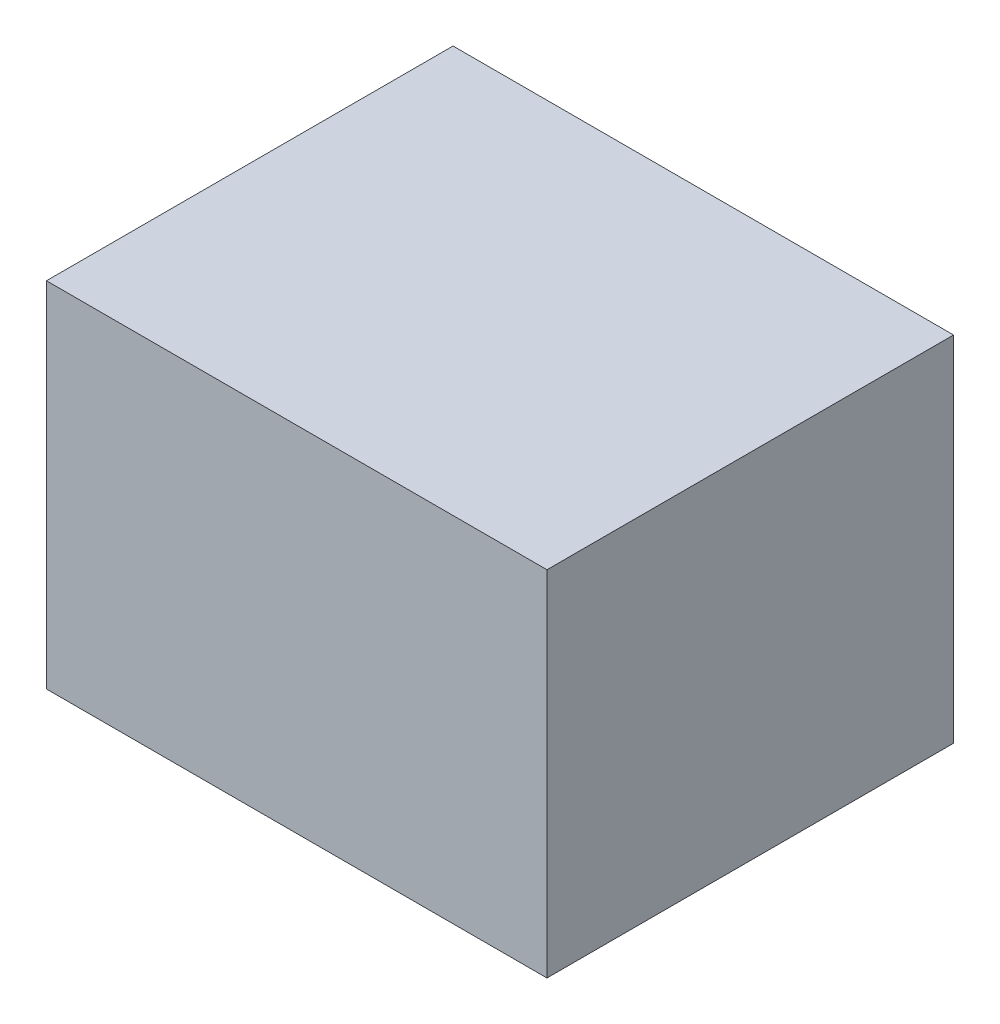
SolidWorks part; units mm, degrees
ref_plane "Front Plane" through (0, 0, 0) normal (0, 0, 1) x (1, 0, 0)
ref_plane "Top Plane" through (0, 0, 0) normal (0, 1, 0) x (1, 0, 0)
ref_plane "Right Plane" through (0, 0, 0) normal (1, 0, 0) x (0, 0, -1)
sketch "Sketch1" plane through (0, 0, 0) normal (0, 1, 0) x (1, 0, 0)
  line L1 (0, 0) -> (36.4531, 0)
  line L2 (0, 0) -> (0, 29.6127)
  line L3 (0, 29.6127) -> (36.4531, 29.6127)
  line L4 (36.4531, 0) -> (36.4531, 29.6127)
extrude "Boss-Extrude1" add sketch "Sketch1" along normal blind 25.7503
sketch "Sketch3" plane through (0, 0, 0) normal (0, 0, 1) x (1, 0, 0)
  line L1 (6.56, 20.699) -> (29.8931, 20.699)
  line L2 (6.56, 20.699) -> (6.56, 4.6431)
  line L3 (6.56, 4.6431) -> (29.8931, 4.6431)
  line L4 (29.8931, 20.699) -> (29.8931, 4.6431)
